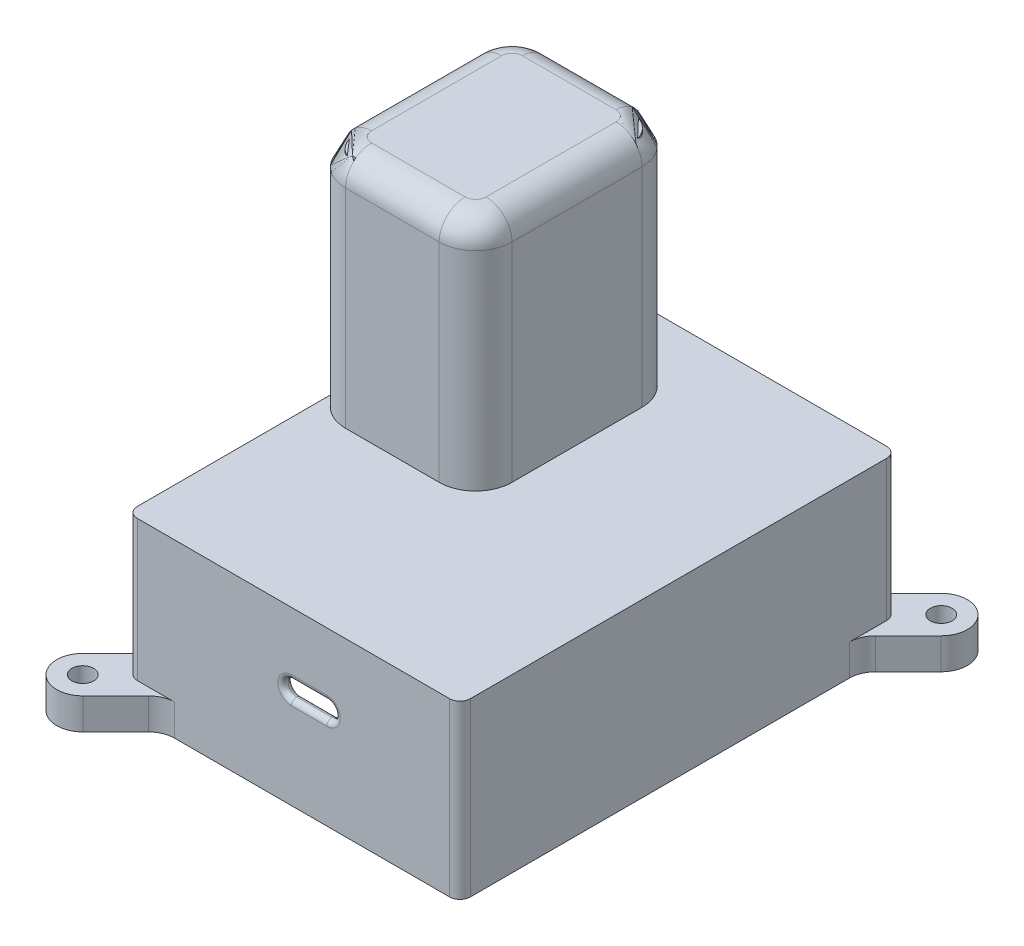
SolidWorks part; units mm, degrees
ref_plane "Front Plane" through (0, 0, 0) normal (0, 0, 1) x (1, 0, 0)
ref_plane "Top Plane" through (0, 0, 0) normal (0, 1, 0) x (1, 0, 0)
ref_plane "Right Plane" through (0, 0, 0) normal (1, 0, 0) x (0, 0, -1)
sketch "Sketch1" plane through (0, 0, 0) normal (0, 1, 0) x (1, 0, 0)
  line L0 (0, 0) -> (60, 0)
  line L1 (60, 0) -> (60, -80)
  line L2 (60, -80) -> (0, -80)
  line L3 (0, -80) -> (0, 0)
  line L4 (-2, -82) -> (-2, 2)
  line L5 (-2, 2) -> (62, 2)
  line L6 (62, 2) -> (62, -82)
  line L7 (62, -82) -> (-2, -82)
  dimension "D1" = 60
  dimension "D2" = 80
  dimension "D3" = 2
extrude "Boss-Extrude1" add sketch "Sketch1" along normal blind 30
ref_plane "HOLE_MIRROR_PLANE" through (-0.3013, 0, 0.2296) normal (0.7954, 0, -0.606) x (-0.606, 0, -0.7954)
sketch "Sketch2" plane through (0, 0, 0) normal (0, 1, 0) x (1, 0, 0)
  line L0 (-2, -82) -> (-6.2426, -86.2426) construction
  line L1 (62, 2) -> (66.2426, 6.2426) construction
  line L2 (69.7782, 2.7071) -> (62, -5.0711)
  line L3 (62.7071, 2.7071) -> (69.7782, 2.7071)
  line L4 (62, -82) -> (62, 2) construction
  line L5 (62, -5.0711) -> (60, 0)
  line L7 (66.2426, 6.2426) -> (69.7782, 2.7071) construction
  line L8 (66.2426, 6.2426) -> (62.8613, 9.9259) construction
  line L9 (62, 2) -> (-2, 2) construction
  line L10 (54.9289, 2) -> (62.8613, 9.9259)
  line L11 (62.8613, 9.9259) -> (62.7071, 2.7071)
  line L12 (60, 0) -> (54.9289, 2)
  line L13 (-6.2426, -86.2426) -> (-2.7071, -89.7782) construction
  line L14 (-6.2426, -86.2426) -> (-9.7782, -82.7071) construction
  line L15 (-2.7071, -89.7782) -> (5.0711, -82)
  line L16 (-2, -82) -> (62, -82) construction
  line L17 (5.0711, -82) -> (0, -80)
  line L18 (-9.7782, -82.7071) -> (-2, -74.9289)
  line L19 (-2, 2) -> (-2, -82) construction
  line L20 (-2, -74.9289) -> (0, -80)
  line L21 (-9.7782, -82.7071) -> (-2.7071, -82.7071)
  line L22 (-2.7071, -82.7071) -> (-2.7071, -89.7782)
  circle A6 centre (66.2426, 6.2426) radius 2.1
  circle A7 centre (66.2426, 6.2426) radius 5
  circle A8 centre (-6.2426, -86.2426) radius 2.1
  circle A9 centre (-6.2426, -86.2426) radius 5
  dimension "D3" = 4.2
  dimension "D4" = 6
  dimension "D2" = 10
  dimension "D5" = 10
  dimension "D6" = 4.2
  dimension "D1" = 6
extrude "Boss-Extrude2" add sketch "Sketch2" along normal blind 6 contours L21 A9 L22 A8 | A9 L15 L17 L20 L18 | L22 A9 | L21 A9 | A7 L10 L12 L5 L2 | L3 A7 | L10 A7 L11 | L3 A7 L11 A6 | L3 L2 L5 L12 L10 L11 region at (66.2426, 0, -2.1133) region at (61.3999, 0, -1.3971) region at (66.2426, 0, -2.8278) region at (62.159, 0, -6.3293) region at (-1.3994, 0, 81.3994) region at (-9.6928, 0, 89.6928) region at (-2.1133, 0, 86.2426) region at (-6.2426, 0, 82.1133)
ref_plane "USBC_HOLE_PLANE" through (0, 0, 82) normal (0, 0, 1) x (1, 0, 0)
sketch "Sketch4" plane through (0, 0, 82) normal (0, 0, 1) x (1, 0, 0)
  line L0 (33.0013, 0) -> (33.0013, 17.6) construction
  line L1 (5.0711, 0) -> (62, 0) construction
  line L2 (33.0013, 17.6) -> (33.0013, 19.2) construction
  line L3 (33.0013, 19.2) -> (28.0013, 19.2) construction
  line L4 (33.0013, 19.2) -> (33.0013, 20.8) construction
  line L5 (28.0013, 19.2) -> (29.6013, 19.2) construction
  line L6 (33.0013, 20.8) -> (29.6013, 20.8)
  line L7 (33.0013, 17.6) -> (29.6013, 17.6)
  line L8 (33.0013, 19.2) -> (38.0013, 19.2) construction
  line L9 (38.0013, 19.2) -> (36.4013, 19.2) construction
  line L10 (33.0013, 20.8) -> (36.4013, 20.8)
  line L11 (33.0013, 17.6) -> (36.4013, 17.6)
  arc A0 (29.6013, 17.6) -> (29.6013, 20.8) centre (29.6013, 19.2) cw
  arc A1 (36.4013, 20.8) -> (36.4013, 17.6) centre (36.4013, 19.2) cw
  dimension "D1" = 17.6
  dimension "D2" = 1.6
  dimension "D3" = 5
  dimension "D4" = 1.6
  dimension "D5" = 1.6
  dimension "D6" = 5
  dimension "D7" = 1.6
extrude "Cut-Extrude1" cut sketch "Sketch4" against normal blind 30
fillet "Fillet2" radius 1 4 edges at (28.0013, 19.2, 82) (33.0013, 20.8, 82) (38.0013, 19.2, 82) (33.0013, 17.6, 82)
fillet "Fillet7" radius 2 8 edges at (0, 15, 80) (60, 15, 80) (60, 15, 0) (0, 15, 0) (62, 15, 82) (-2, 15, -2) (-2, 18, 82) (62, 18, -2)
fillet "Fillet8" radius 1.1 4 edges at (38.0013, 19.2, 80) (33.0013, 20.8, 80) (28.0013, 19.2, 80) (33.0013, 17.6, 80)
fillet "Fillet9" radius 5 4 edges at (62, 3, 5.0711) (54.9289, 3, -2) (-2, 3, 74.9289) (5.0711, 3, 82)
sketch "Sketch5" plane through (0, 30, 0) normal (0, 1, 0) x (1, 0, 0)
  line L0 (-2, 0) -> (-2, -10) construction
  line L1 (-2, 0) -> (-2, -80) construction
  line L2 (-2, -10) -> (-2, -45) construction
  line L3 (-2, -45) -> (-2, -80)
  line L4 (0, -82) -> (60, -82)
  line L5 (0, -82) -> (-2, -82)
  line L6 (-2, -82) -> (-2, -80)
  line L7 (62, -80) -> (62, 0)
  line L8 (60, -82) -> (62, -82)
  line L9 (62, -82) -> (62, -80)
  line L10 (0, 2) -> (60, 2)
  line L11 (60, 2) -> (62, 2)
  line L12 (62, 2) -> (62, 0)
  line L13 (0, 2) -> (-2, 2)
  line L14 (-2, 2) -> (-2, 0)
  line L15 (-2, 0) -> (-2, -10)
  line L16 (-2, -10) -> (28, -10)
  line L17 (28, -10) -> (28, -45)
  line L18 (28, -45) -> (-2, -45)
  line L19 (-2, -10) -> (-2, -45)
  line L20 (0, -45) -> (0, -10)
  line L21 (0, -2) -> (0, -78) construction
  line L22 (0, -10) -> (-2, -10)
  line M19 (-2, 0) -> (-2, -80)
  arc M20 (-2, -80) -> (0, -82) centre (0, -80) ccw
  line M21 (0, -82) -> (60, -82)
  arc M22 (60, -82) -> (62, -80) centre (60, -80) ccw
  line M23 (62, -80) -> (62, 0)
  arc M24 (62, 0) -> (60, 2) centre (60, 0) ccw
  line M25 (60, 2) -> (0, 2)
  arc M26 (0, 2) -> (-2, 0) centre (0, 0) ccw
  line M27 (0, -78) -> (0, -2)
  arc M28 (0, -2) -> (2, 0) centre (2, -2) cw
  line M29 (2, 0) -> (58, 0)
  arc M30 (58, 0) -> (60, -2) centre (58, -2) cw
  line M31 (60, -2) -> (60, -78)
  arc M32 (60, -78) -> (58, -80) centre (58, -78) cw
  line M33 (58, -80) -> (2, -80)
  arc M34 (2, -80) -> (0, -78) centre (2, -78) cw
  dimension "D1" = 10
  dimension "D2" = 35
  dimension "D3" = 30
extrude "Boss-Extrude3" add sketch "Sketch5" along normal blind 3 contours L18 L16 M27 M19 | L17 L18 L16 M27 M34 M33 M32 M31 M30 M29 M28 | L18 L16 M27 M19 M20 M21 M22 M23 M24 M25 M26 M28 M29 M30 M31 M32 M33 M34 region at (-1, 30, 46.056) region at (-1, 30, 27.5) region at (34.1084, 30, 43.2097)
sketch "Sketch6" plane through (0, 33, 0) normal (0, 1, 0) x (1, 0, 0)
  line L0 (5, -10) -> (14, -10)
  line L1 (0, -10) -> (28, -10) construction
  line L2 (14, -10) -> (23, -10)
  line L3 (28, -15) -> (28, -40)
  line L4 (23, -45) -> (14, -45)
  line L5 (28, -45) -> (0, -45) construction
  line L6 (14, -45) -> (5, -45)
  line L7 (0, -40) -> (0, -15)
  line L12 (-2, -40) -> (-2, -15)
  line L13 (5, -8) -> (14, -8)
  line L14 (14, -8) -> (23, -8)
  line L15 (30, -15) -> (30, -40)
  line L16 (23, -47) -> (14, -47)
  line L17 (14, -47) -> (5, -47)
  arc A0 (0, -40) -> (5, -45) centre (5, -40) ccw
  arc A1 (23, -45) -> (28, -40) centre (23, -40) ccw
  arc A2 (28, -15) -> (23, -10) centre (23, -15) ccw
  arc A3 (0, -15) -> (5, -10) centre (5, -15) cw
  arc A8 (-2, -15) -> (5, -8) centre (5, -15) cw
  arc A9 (30, -15) -> (23, -8) centre (23, -15) ccw
  arc A10 (23, -47) -> (30, -40) centre (23, -40) ccw
  arc A11 (-2, -40) -> (5, -47) centre (5, -40) ccw
  point P15 (0, -45)
  point P18 (28, -45)
  point P21 (28, -10)
  point P24 (0, -10)
  dimension "D1" = 5
  dimension "D2" = 2
extrude "Boss-Extrude4" add sketch "Sketch6" along normal blind 45 and the other way blind 3
sketch "Sketch7" plane through (0, 78, 0) normal (0, 1, 0) x (1, 0, 0)
  line L0 (0, -15) -> (0, -40)
  line L1 (0, -40) -> (0.0503, -44.9497)
  line L2 (0.0503, -44.9497) -> (4.2929, -44.9497)
  line L5 (28, -40) -> (28, -15)
  line L6 (28, -15) -> (27.9497, -10.0503)
  line L7 (27.9497, -10.0503) -> (23, -10)
  line L8 (23, -10) -> (5, -10)
  line L9 (23, -10) -> (5, -10) construction
  line L12 (4.2929, -44.9497) -> (5, -45)
  line L13 (5, -45) -> (23, -45)
  line L14 (23, -45) -> (25.0123, -45)
  line L15 (25.0123, -45) -> (26.6261, -43.8962)
  line L16 (26.6261, -43.8962) -> (28, -42.9564)
  line L17 (28, -42.9564) -> (28, -40)
  line L18 (0, -15) -> (-0.2325, -13.2579)
  line L19 (-0.2325, -13.2579) -> (0.3978, -11.7488)
  line L20 (0.3978, -11.7488) -> (1.1619, -10.6982)
  line L21 (1.1619, -10.6982) -> (2.4159, -9.8405)
  line L22 (2.4159, -9.8405) -> (3.9041, -9.6419)
  line L23 (3.9041, -9.6419) -> (5, -10)
  arc A0 (-2, -40) -> (5, -47) centre (5, -40) ccw construction
  arc A1 (0, -40) -> (5, -45) centre (5, -40) ccw construction
  arc A2 (30, -15) -> (23, -8) centre (23, -15) ccw construction
  arc A3 (5, -10) -> (0, -15) centre (5, -15) ccw construction
extrude "Boss-Extrude6" add sketch "Sketch7" against normal blind 2
fillet "Fillet11" radius 5 8 edges at (14, 78, 8) (27.9497, 78, 10.0503) (30, 78, 27.5) (27.9497, 78, 44.9497) (14, 78, 47) (0.0503, 78, 44.9497) (-2, 78, 27.5) (0.0503, 78, 10.0503)
fillet "Fillet12" radius 2 9 edges at (0, 30, 6) (0.5858, 30, 0.5858) (30, 30, 0) (59.4142, 30, 0.5858) (60, 30, 40) (59.4142, 30, 79.4142) (30, 30, 80) (0.5858, 30, 79.4142) (0, 30, 61.5)
